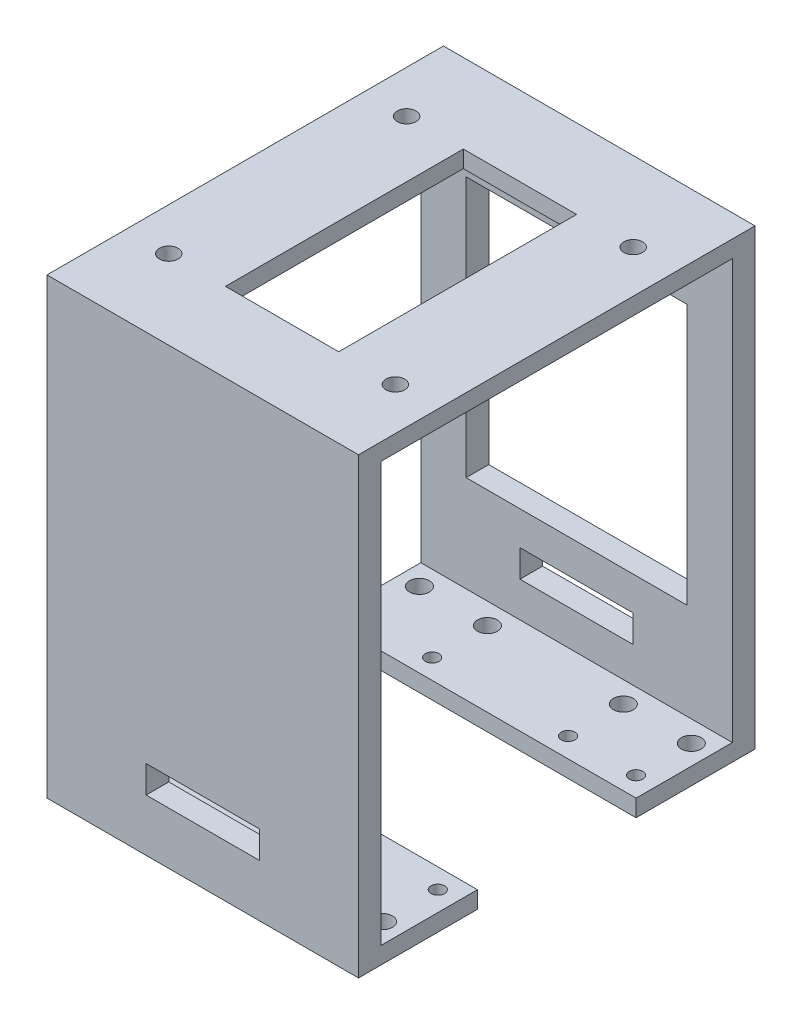
SolidWorks part; units mm, degrees
ref_plane "Front Plane" through (0, 0, 0) normal (0, 0, 1) x (1, 0, 0)
ref_plane "Top Plane" through (0, 0, 0) normal (0, 1, 0) x (1, 0, 0)
ref_plane "Right Plane" through (0, 0, 0) normal (1, 0, 0) x (0, 0, -1)
sketch "Sketch1" plane through (0, 0, 0) normal (0, 1, 0) x (1, 0, 0)
  line L0 (0, 0) -> (0, -14.43) construction
  line L1 (-37.5, 20) -> (37.5, 20)
  line L2 (-37.5, 20) -> (-37.5, -20)
  line L3 (-37.5, -20) -> (37.5, -20)
  line L4 (37.5, 20) -> (37.5, -20)
  line L5 (-37.5, 20) -> (37.5, -20) construction
  line L6 (-37.5, -20) -> (37.5, 20) construction
  line L7 (0, 0) -> (6.508, 0) construction
  line L8 (-5, 10) -> (5, 10)
  line L9 (-5, 10) -> (-5, -10)
  line L10 (-5, -10) -> (5, -10)
  line L11 (5, 10) -> (5, -10)
  line L12 (-5, 10) -> (5, -10) construction
  line L13 (-5, -10) -> (5, 10) construction
  circle A0 centre (-21, 0) radius 5
  circle A1 centre (-30, 8.25) radius 1.7
  circle A2 centre (-12, 8.25) radius 1.7
  circle A3 centre (-12, -8.25) radius 1.7
  circle A4 centre (-30, -8.25) radius 1.7
  circle A5 centre (12, 8.25) radius 1.7
  circle A6 centre (12, -8.25) radius 1.7
  circle A7 centre (21, 0) radius 5
  circle A8 centre (30, -8.25) radius 1.7
  circle A9 centre (30, 8.25) radius 1.7
  point P0 (0, 0)
  dimension "D3" = 10
  dimension "D4" = 16.5
  dimension "D5" = 16.5
  dimension "D6" = 18
  dimension "D9" = 10
  dimension "D11" = 20
  dimension "D13" = 7.5
  dimension "D17" = 3.4
  dimension "D19" = 11.75
  dimension "D20" = 11.75
  dimension "D1" = 75
  dimension "D2" = 40
  dimension "D10" = 10
  dimension "D7" = 2
  dimension "D8" = 2
extrude "Boss-Extrude1" add sketch "Sketch1" along normal blind 3
sketch "Sketch2" plane through (0, 3, 0) normal (0, 1, 0) x (1, 0, 0)
  line L0 (-37.5, 20) -> (-37.5, -20) construction
  line L1 (-33.5, 14) -> (33.5, 14)
  line L2 (-33.5, 14) -> (-33.5, -14)
  line L3 (-33.5, -14) -> (33.5, -14)
  line L4 (33.5, 14) -> (33.5, -14)
  line L5 (37.5, -20) -> (37.5, 20) construction
  line L6 (37.5, 20) -> (-37.5, 20) construction
  line L7 (-37.5, -20) -> (37.5, -20) construction
  dimension "D1" = 4
  dimension "D2" = 4
  dimension "D3" = 6
  dimension "D4" = 6
extrude "Cut-Extrude1" cut sketch "Sketch2" against normal through all both and the other way through all
sketch "Sketch3" plane through (0, 3, 0) normal (0, 1, 0) x (1, 0, 0)
  line L1 (37.5, 20) -> (-37.5, 20)
  line L2 (37.5, 20) -> (37.5, 35)
  line L3 (37.5, 35) -> (-37.5, 35)
  line L4 (-37.5, 20) -> (-37.5, 35)
  line L5 (-37.5, -20) -> (37.5, -20)
  line L6 (-37.5, -20) -> (-37.5, -35)
  line L7 (-37.5, -35) -> (37.5, -35)
  line L8 (37.5, -20) -> (37.5, -35)
  line L10 (-37.5, 20) -> (-33.5, 20)
  line L11 (-37.5, 20) -> (-37.5, -20)
  line L12 (-37.5, -20) -> (-33.5, -20)
  line L13 (-33.5, 20) -> (-33.5, -20)
  line L14 (37.5, 20) -> (33.5, 20)
  line L15 (37.5, 20) -> (37.5, -20)
  line L16 (37.5, -20) -> (33.5, -20)
  line L17 (33.5, 20) -> (33.5, -20)
  line M3 (-33.5, -14) -> (-33.5, 14)
  line M5 (33.5, 14) -> (33.5, -14)
  line M11 (37.5, -20) -> (37.5, 20)
  line M12 (37.5, 20) -> (-37.5, 20)
  line M13 (-37.5, 20) -> (-37.5, -20)
  line M14 (-37.5, -20) -> (37.5, -20)
  dimension "D1" = 15
  dimension "D2" = 15
extrude "Boss-Extrude3" add sketch "Sketch3" along normal blind 110 and the other way blind 3 contours L8 L5 L6 L7 M14 | L4 L1 L2 L3 M12 | L17 M12 M5 M14 M11 | L13 L1 M13 M14 M3 region at (35.5, 3, 0) region at (0, 3, -27.5) region at (0, 3, 27.5) region at (-35.5, 3, 0)
sketch "Sketch6" plane through (0, 3, 0) normal (0, 1, 0) x (1, 0, 0)
  line L0 (-37.5, -35) -> (37.5, -35) construction
  line L1 (-33.5, -20) -> (33.5, -20)
  line L2 (-33.5, -20) -> (-33.5, -31)
  line L3 (-33.5, -31) -> (33.5, -31)
  line L4 (33.5, -20) -> (33.5, -31)
  line L5 (33.5, 20) -> (-33.5, 20)
  line L6 (33.5, 20) -> (33.5, 31)
  line L7 (33.5, 31) -> (-33.5, 31)
  line L8 (-33.5, 20) -> (-33.5, 31)
  line L9 (37.5, 35) -> (-37.5, 35) construction
  dimension "D1" = 4
  dimension "D2" = 4
extrude "Cut-Extrude4" cut sketch "Sketch6" along normal through all
sketch "Sketch7" plane through (-37.5, 0, 0) normal (-1, 0, 0) x (0, 0, 1)
  line L0 (35, 0) -> (35, 113) construction
  line L1 (-35, 113) -> (35, 113)
  line L2 (-35, 113) -> (-35, 76)
  line L3 (-35, 76) -> (35, 76)
  line L4 (35, 113) -> (35, 76)
  dimension "D1" = 37
extrude "Boss-Extrude4" add sketch "Sketch7" along normal blind 45
ref_plane "Plane1" through (0, 0, 0) normal (1, 0, 0) x (0, 0, -1)
mirror "Mirror2" about plane through (0, 0, 0) normal (1, 0, 0) of "Boss-Extrude4"
sketch "Sketch8" plane through (0, 113, 0) normal (0, 1, 0) x (1, 0, 0)
  line L0 (-82.5, -35) -> (-82.5, 35) construction
  line L1 (-33.5, 31) -> (-78.5, 31)
  line L2 (-33.5, 31) -> (-33.5, -31)
  line L3 (-33.5, -31) -> (-78.5, -31)
  line L4 (-78.5, 31) -> (-78.5, -31)
  line L5 (33.5, -31) -> (78.5, -31)
  line L6 (33.5, -31) -> (33.5, 31)
  line L7 (33.5, 31) -> (78.5, 31)
  line L8 (78.5, -31) -> (78.5, 31)
  line L9 (82.5, -35) -> (82.5, 35) construction
  dimension "D1" = 4
  dimension "D2" = 4
extrude "Cut-Extrude6" cut sketch "Sketch8" against normal blind 29
sketch "Sketch9" plane through (-82.5, 0, 0) normal (-1, 0, 0) x (0, 0, 1)
  line L18 (-31, 84) -> (31, 84) construction
  line L19 (-19, 84) -> (19, 84)
  line L20 (-19, 84) -> (-19, 112.5)
  line L21 (-19, 112.5) -> (19, 112.5)
  line L22 (19, 84) -> (19, 112.5)
  line L25 (-31, 84) -> (-31, 113) construction
  dimension "D1" = 38
  dimension "D2" = 12
  dimension "D3" = 28.5
sketch "Sketch11" plane through (0, 0, 35) normal (0, 0, 1) x (1, 0, 0)
  line L0 (82.5, 76) -> (82.5, 113) construction
  line L1 (-82.5, 76) -> (-37.5, 76)
  line L2 (-82.5, 76) -> (-82.5, 80)
  line L3 (-82.5, 80) -> (-37.5, 80)
  line L4 (-37.5, 76) -> (-37.5, 80)
  line L5 (37.5, 76) -> (82.5, 76)
  line L6 (37.5, 76) -> (37.5, 80)
  line L7 (37.5, 80) -> (82.5, 80)
  line L8 (82.5, 76) -> (82.5, 80)
  line L11 (-78.5, 84) -> (-33.5, 84) construction
  line L12 (33.5, 84) -> (78.5, 84) construction
  dimension "D1" = 4
  dimension "D2" = 4
extrude "Cut-Extrude9" cut sketch "Sketch11" against normal through all
extrude "Cut-Extrude10" cut sketch "Sketch9" against normal through all
sketch "Sketch13" plane through (0, 84, 0) normal (0, 1, 0) x (1, 0, 0)
  line L0 (-78.5, 31) -> (-78.5, -31) construction
  line L1 (-57, 19) -> (-52, 19)
  line L2 (-57, 19) -> (-57, -19)
  line L3 (-57, -19) -> (-52, -19)
  line L4 (-52, 19) -> (-52, -19)
  line L7 (78.5, 31) -> (-78.5, 31) construction
  line L13 (-57, -19) -> (-57, 19)
  line L17 (-82.5, -19) -> (-107.5, -19)
  line L18 (-82.5, -19) -> (-82.5, 19)
  line L19 (-82.5, 19) -> (-107.5, 19)
  line L20 (-107.5, -19) -> (-107.5, 19)
  line L21 (-107.5, 19) -> (-61, 19)
  line L22 (-107.5, 19) -> (-107.5, -19)
  line L23 (-107.5, -19) -> (-61, -19)
  line L24 (-61, 19) -> (-61, -19)
  dimension "D1" = 21.5
  dimension "D2" = 5
  dimension "D3" = 38
  dimension "D4" = 12
  dimension "D5" = 25
  dimension "D6" = 46.5
extrude "Boss-Extrude5" add sketch "Sketch13" along normal blind 32 contours L4 L1 L2 L3 region at (-54.5, 84, 0)
sketch "Sketch14" plane through (-57, 0, 0) normal (-1, 0, 0) x (0, 0, 1)
  line L0 (-19, 116) -> (-19, 84) construction
  line L4 (19, 112.5) -> (-19, 112.5) construction
  circle A0 centre (0, 98.25) radius 5
  circle A1 centre (-9, 106.5) radius 1.7
  circle A2 centre (9, 106.5) radius 1.7
  circle A3 centre (9, 90) radius 1.7
  circle A4 centre (-9, 90) radius 1.7
  dimension "D1" = 19
  dimension "D2" = 9
  dimension "D3" = 10
  dimension "D6" = 3.4
  dimension "D7" = 14.25
  dimension "D8" = 16.5
  dimension "D9" = 18
  dimension "D10" = 8.25
  dimension "D4" = 2
  dimension "D5" = 2
extrude "Cut-Extrude11" cut sketch "Sketch14" against normal blind 32
mirror "Mirror4" about plane through (0, 0, 0) normal (1, 0, 0) of "Boss-Extrude5", "Cut-Extrude11"
sketch "Sketch15" plane through (0, 113, 0) normal (0, 1, 0) x (1, 0, 0)
  line L1 (-82.5, 35) -> (82.5, 35)
  line L2 (-82.5, 35) -> (-82.5, -35)
  line L3 (-82.5, -35) -> (82.5, -35)
  line L4 (82.5, 35) -> (82.5, -35)
  line L5 (-78.5, 31) -> (78.5, 31)
  line L6 (-78.5, 31) -> (-78.5, -31)
  line L7 (-78.5, -31) -> (78.5, -31)
  line L8 (78.5, 31) -> (78.5, -31)
extrude "Boss-Extrude6" add sketch "Sketch15" along normal blind 3
sketch "Sketch16" plane through (0, 0, 35) normal (0, 0, 1) x (1, 0, 0)
  line L1 (-10, 14.0464) -> (10, 14.0464)
  line L2 (-10, 14.0464) -> (-10, 9.2258)
  line L3 (-10, 9.2258) -> (10, 9.2258)
  line L4 (10, 14.0464) -> (10, 9.2258)
  line L5 (-37.5, 0) -> (-37.5, 80) construction
  dimension "D1" = 20
  dimension "D2" = 27.5
extrude "Cut-Extrude12" cut sketch "Sketch16" against normal through all
sketch "Sketch18" plane through (0, 0, 35) normal (0, 0, 1) x (1, 0, 0)
  line L0 (57, 116) -> (57, 84) construction
  line L2 (33.5, 84) -> (78.5, 84) construction
  circle A0 centre (67.75, 100) radius 5
  dimension "D1" = 10.75
  dimension "D2" = 16
  dimension "D3" = 10
extrude "Cut-Extrude14" cut sketch "Sketch18" against normal through all
mirror "Mirror5" about plane through (0, 0, 0) normal (1, 0, 0) of "Cut-Extrude14"
mirror "Mirror6" about plane through (0, 116, 0) normal (0, 1, 0) of "Mirror4"
sketch "Sketch19" plane through (82.5, 0, 0) normal (1, 0, 0) x (0, 0, -1)
  line L0 (19, 148) -> (19, 84) construction
  line L1 (-19, 112.5) -> (19, 112.5)
  line L2 (-19, 112.5) -> (-19, 116)
  line L3 (-19, 116) -> (19, 116)
  line L4 (19, 112.5) -> (19, 116)
extrude "Cut-Extrude15" cut sketch "Sketch19" against normal blind 10
mirror "Mirror7" about plane through (0, 0, 0) normal (1, 0, 0) of "Cut-Extrude15"
sketch "Sketch20" plane through (0, 3, 0) normal (0, 1, 0) x (1, 0, 0)
  line L0 (33.5, 31) -> (-33.5, 31) construction
  line L1 (-5, -10) -> (5, -10)
  line L2 (-5, -10) -> (-5, 10)
  line L3 (-5, 10) -> (5, 10)
  line L4 (5, -10) -> (5, 10)
  line L5 (-5, -10) -> (5, 10) construction
  line L6 (-5, 10) -> (5, -10) construction
  line L7 (0, 0) -> (0, 17.5) construction
  line L8 (-37.5, 20) -> (37.5, 20)
  line L9 (-37.5, 20) -> (-37.5, -20)
  line L10 (-37.5, -20) -> (37.5, -20)
  line L11 (37.5, 20) -> (37.5, -20)
  line L12 (-37.5, 20) -> (37.5, -20) construction
  line L13 (-37.5, -20) -> (37.5, 20) construction
  line L14 (0, -34.1) -> (0, 34.1) construction
  circle A1 centre (-12, 17.5) radius 1.2
  circle A2 centre (-12, -17.5) radius 1.2
  circle A3 centre (-24, -17.5) radius 1.2
  circle A4 centre (-24, 17.5) radius 1.2
  circle A5 centre (12, -17.5) radius 1.2
  circle A6 centre (24, -17.5) radius 1.2
  circle A7 centre (12, 17.5) radius 1.2
  circle A8 centre (24, 17.5) radius 1.2
  point P2 (0, 0)
  point P10 (0, 0)
  dimension "D1" = 7
  dimension "D2" = 10
  dimension "D4" = 2.5
  dimension "D7" = 35
  dimension "D8" = 7
  dimension "D9" = 2.4
  dimension "D11" = 12
  dimension "D3" = 21
  dimension "D5" = 75
  dimension "D6" = 40
  dimension "D10" = 2
extrude "Cut-Extrude16" cut sketch "Sketch20" against normal blind 10 contours A4 | A1 | A7 | A3 | A2 | A8 | A5 | A6 region at (-12, 3, -17.5) region at (-12, 3, 17.5) region at (-24, 3, 17.5) region at (-24, 3, -17.5) region at (12, 3, 17.5) region at (24, 3, 17.5) region at (12, 3, -17.5) region at (24, 3, -17.5)
sketch "Sketch21" plane through (0, 0, 35) normal (0, 0, 1) x (1, 0, 0)
  line L0 (0, -34.1) -> (0, 34.1) construction
  line L1 (37.5, 0) -> (27.5, 0)
  line L2 (37.5, 0) -> (37.5, 80)
  line L3 (37.5, 80) -> (27.5, 80)
  line L4 (27.5, 0) -> (27.5, 80)
  line L5 (-27.5, 0) -> (-27.5, 80)
  line L6 (-37.5, 80) -> (-27.5, 80)
  line L7 (-37.5, 0) -> (-37.5, 80)
  line L8 (-37.5, 0) -> (-27.5, 0)
  dimension "D1" = 10
  dimension "D2" = 80
extrude "Cut-Extrude17" cut sketch "Sketch21" against normal through all
sketch "Sketch22" plane through (0, 0, 35) normal (0, 0, 1) x (1, 0, 0)
  line L1 (82.5, 80) -> (-90.2391, 80)
  line L2 (82.5, 80) -> (82.5, 155.8432)
  line L3 (82.5, 155.8432) -> (-90.2391, 155.8432)
  line L4 (-90.2391, 80) -> (-90.2391, 155.8432)
extrude "Cut-Extrude18" cut sketch "Sketch22" against normal through all
sketch "Sketch23" plane through (0, 80, 0) normal (0, 1, 0) x (1, 0, 0)
  line L5 (-27.5, 35) -> (27.5, 35)
  line L6 (-27.5, 35) -> (-27.5, -35)
  line L7 (-27.5, -35) -> (27.5, -35)
  line L8 (27.5, 35) -> (27.5, -35)
extrude "Boss-Extrude7" add sketch "Sketch23" against normal blind 3
sketch "Sketch24" plane through (0, 80, 0) normal (0, 1, 0) x (1, 0, 0)
  line L0 (-27.5, 35) -> (27.5, 35) construction
  line L1 (-27.5, 35) -> (-27.5, -35) construction
  line L2 (0, -55) -> (0, 55) construction
  circle A0 centre (0, 0) radius 10
  circle A1 centre (-20, 21) radius 1.65
  circle A2 centre (-20, -21) radius 1.65
  circle A3 centre (20, -21) radius 1.65
  circle A4 centre (20, 21) radius 1.65
  point P0 (0, 0)
  dimension "D2" = 35
  dimension "D1" = 21
  dimension "D3" = 27.5
  dimension "D4" = 20
  dimension "D5" = 3.3
  dimension "D6" = 3.3
  dimension "D7" = 21
  dimension "D8" = 20
extrude "Cut-Extrude19" cut sketch "Sketch24" against normal blind 3
sketch "Sketch25" plane through (0, 0, 0) normal (0, -1, 0) x (1, 0, 0)
  line L2 (-27.5, 14) -> (-27.5, 35) construction
  line L3 (0, 0) -> (35.9025, 0) construction
  line L4 (0, 0) -> (0, -14.2045) construction
  line L5 (0, -55) -> (0, 55) construction
  circle A0 centre (-24, 27.2549) radius 1.75
  circle A1 centre (12, -27.2549) radius 1.75
  circle A2 centre (24, -27.2549) radius 1.75
  circle A4 centre (12, 27.2549) radius 1.75
  circle A5 centre (-12, 27.2549) radius 1.75
  circle A6 centre (-24, -27.2549) radius 1.75
  circle A7 centre (-12, -27.2549) radius 1.75
  circle A8 centre (24, 27.2549) radius 1.75
  dimension "D1" = 3.5
  dimension "D2" = 3.5
  dimension "D3" = 2
extrude "Cut-Extrude20" cut sketch "Sketch25" against normal blind 10
sketch "Sketch27" plane through (0, 0, -35) normal (0, 0, -1) x (-1, 0, 0)
  line L0 (27.5, 80) -> (-27.5, 80) construction
  line L1 (-19.5, 66) -> (19.5, 66)
  line L2 (-19.5, 66) -> (-19.5, 20)
  line L3 (-19.5, 20) -> (19.5, 20)
  line L4 (19.5, 66) -> (19.5, 20)
  line L5 (27.5, 0) -> (27.5, 80) construction
  line L6 (-27.5, 80) -> (-27.5, 0) construction
  line L7 (-27.5, 0) -> (27.5, 0) construction
  dimension "D1" = 14
  dimension "D2" = 8
  dimension "D3" = 8
  dimension "D4" = 20
extrude "Cut-Extrude21" cut sketch "Sketch27" against normal blind 4
sketch "Sketch29" plane through (0, 80, 0) normal (0, 1, 0) x (1, 0, 0)
  line L1 (-10, 21) -> (10, 21)
  line L2 (-10, 21) -> (-10, -21)
  line L3 (-10, -21) -> (10, -21)
  line L4 (10, 21) -> (10, -21)
  line L5 (-10, 21) -> (10, -21) construction
  line L6 (-10, -21) -> (10, 21) construction
  point P0 (0, 0)
  dimension "D1" = 20
  dimension "D2" = 42
extrude "Cut-Extrude22" cut sketch "Sketch29" against normal blind 10
